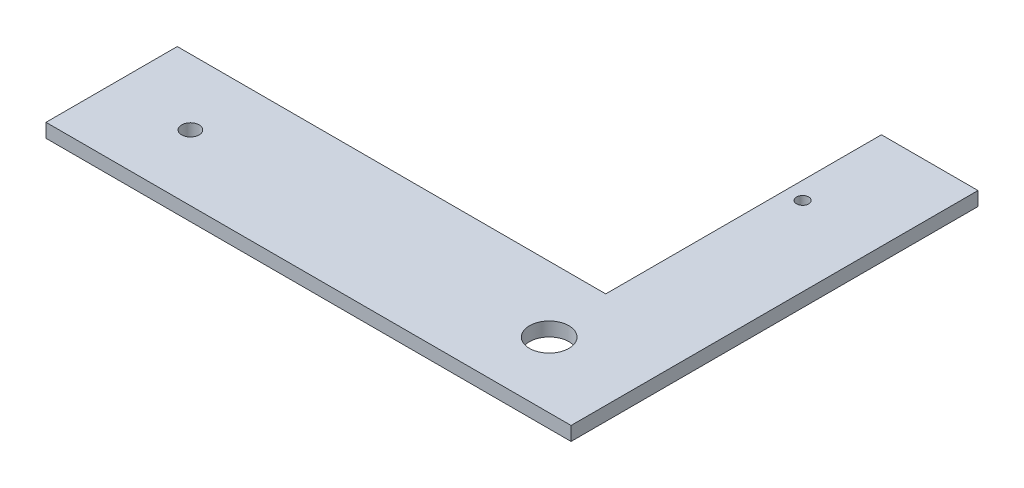
SolidWorks part; units mm, degrees
ref_plane "Front" through (0, 0, 0) normal (0, 0, 1) x (1, 0, 0)
ref_plane "Top" through (0, 0, 0) normal (0, 1, 0) x (1, 0, 0)
ref_plane "Right" through (0, 0, 0) normal (1, 0, 0) x (0, 0, -1)
sketch "Sketch1" plane through (0, 0, 0) normal (0, 1, 0) x (1, 0, 0)
  line L1 (0, 0) -> (120, 0)
  line L2 (0, 0) -> (0, 30)
  line L3 (0, 30) -> (120, 30)
  line L4 (120, 0) -> (120, 30)
  dimension "D1" = 120
  dimension "D2" = 30
extrude "Boss-Extrude1" add sketch "Sketch1" along normal blind 3.175
sketch "Sketch2" plane through (0, 3.175, 0) normal (0, 1, 0) x (1, 0, 0)
  line L0 (0, 30) -> (0, 0) construction
  line L1 (120, 30) -> (0, 30) construction
  line L2 (120, 0) -> (120, 30) construction
  circle A0 centre (18, 15) radius 2
  circle A1 centre (100, 15) radius 4.5
  dimension "D1" = 18
  dimension "D3" = 15
  dimension "D2" = 15
  dimension "D4" = 20
extrude "Cut-Extrude1" cut sketch "Sketch2" against normal blind 3.175
sketch "Sketch3" plane through (0, 0, -30) normal (0, 0, -1) x (-1, 0, 0)
  line L0 (-120, 0) -> (0, 0) construction
  line L1 (-97.9274, 0) -> (-120, 0)
  line L2 (-97.9274, 0) -> (-97.9274, 3.175)
  line L3 (-97.9274, 3.175) -> (-120, 3.175)
  line L4 (-120, 0) -> (-120, 3.175)
  line L5 (-120, 3.175) -> (-120, 0) construction
  line L6 (-120, 3.175) -> (0, 3.175) construction
extrude "Boss-Extrude2" add sketch "Sketch3" along normal blind 63
sketch "Sketch4" plane through (0, 3.175, 0) normal (0, 1, 0) x (1, 0, 0)
  line L0 (97.9274, 93) -> (120, 93) construction
  line L1 (97.9274, 93) -> (97.9274, 30) construction
  circle A0 centre (101.9274, 71) radius 1.3818
  dimension "D1" = 22
  dimension "D2" = 4
extrude "Cut-Extrude2" cut sketch "Sketch4" against normal blind 10
